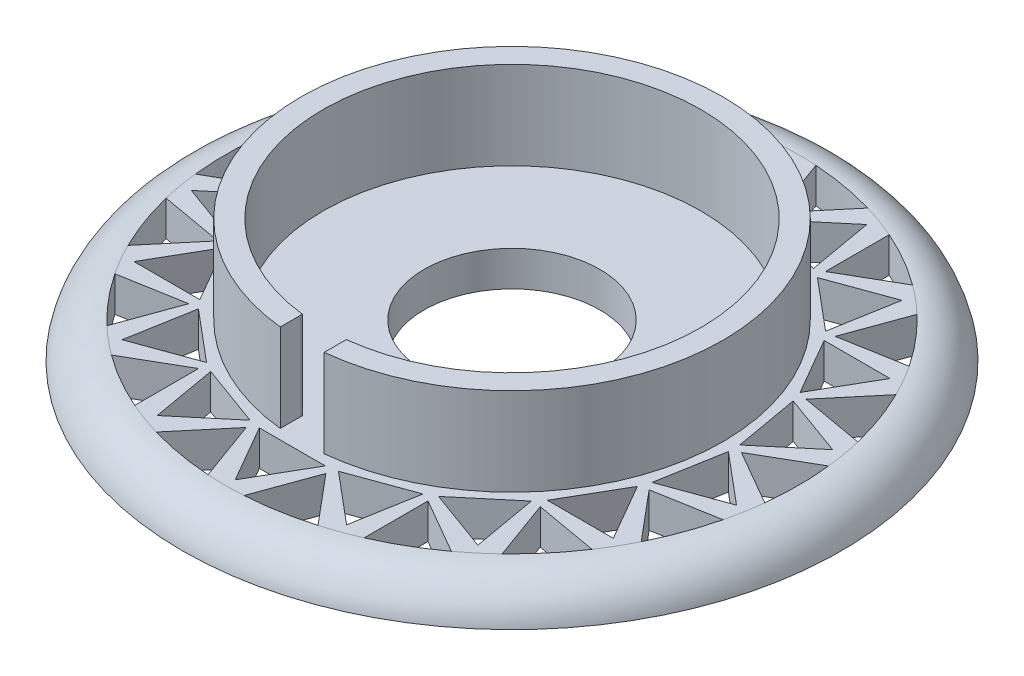
SolidWorks part; units mm, degrees
ref_plane "Front Plane" through (0, 0, 0) normal (0, 0, 1) x (1, 0, 0)
ref_plane "Top Plane" through (0, 0, 0) normal (0, 1, 0) x (1, 0, 0)
ref_plane "Right Plane" through (0, 0, 0) normal (1, 0, 0) x (0, 0, -1)
sketch "Sketch1" plane through (0, 0, 0) normal (0, 1, 0) x (1, 0, 0)
  circle A0 centre (0, 0) radius 75
  dimension "D1" = 150
extrude "Boss-Extrude1" add sketch "Sketch1" along normal blind 8
sketch "Sketch2" plane through (0, 8, 0) normal (0, 1, 0) x (1, 0, 0)
  circle A0 centre (0, 0) radius 43
  circle A1 centre (0, 0) radius 48
  dimension "D1" = 86
  dimension "D2" = 5
extrude "Boss-Extrude3" add sketch "Sketch2" along normal blind 20
sketch "Sketch7" plane through (0, 28, 0) normal (0, 1, 0) x (1, 0, 0)
  line L0 (-5, -43) -> (0, 0)
  line L1 (-5, -43) -> (5, -43)
  line L2 (-5, -43) -> (-5, -48)
  line L3 (-5, -48) -> (5, -48)
  line L4 (5, -43) -> (5, -48)
  line L5 (0, 0) -> (5, -43)
  circle A0 centre (0, 0) radius 43 construction
  circle A1 centre (0, 0) radius 48 construction
  circle M5 centre (0, 0) radius 48
  circle M6 centre (0, 0) radius 43
  dimension "D1" = 10
extrude "Cut-Extrude2" cut sketch "Sketch7" against normal up to surface (20 mm away) contours L4 L1 L2 M5 | L2 L3 M5 | L4 L3 M5 | L5 L1 M6 | L0 L1 M6 region at (-3.7383, 28, 42.9136) region at (0, 28, 45.4571) region at (3.7383, 28, 42.9136) region at (-3.7507, 28, 47.9217) region at (3.7507, 28, 47.9217) up to face at (0, 8, 48)
fillet "Fillet1" radius 10 1 edges at (0, 8, 75)
sketch "Sketch8" plane through (0, 8, 0) normal (0, 1, 0) x (1, 0, 0)
  line L0 (0, 0) -> (-65.202, 0) construction
  line L1 (-52.2117, 0) -> (-65.202, -7.5)
  line L2 (-65.202, -7.5) -> (-65.202, 7.5)
  line L3 (-65.202, 7.5) -> (-52.2117, 0)
  line L4 (-62.0334, 10.9382) -> (-50.5427, 1.2964)
  line L5 (-50.5427, 1.2964) -> (-47.938, 16.0685)
  line L6 (-47.938, 16.0685) -> (-62.0334, 10.9382)
  line L7 (-62.0334, 10.9382) -> (0, 0) construction
  circle A0 centre (0, 0) radius 65.202 construction
  arc A4 (5.2083, -49.728) -> (-5.2083, -49.728) centre (0, 0) ccw
  arc A5 (5.2083, -49.728) -> (-5.2083, -49.728) centre (0, 0) ccw construction
  point P0 (-49.2404, 8.6824)
  circle M10 centre (0, 0) radius 65.202
  dimension "D1" = 15
  dimension "D2" = 10
  dimension "D3" = 2
extrude "Cut-Extrude3" cut sketch "Sketch8" against normal through all contours L3 L1 M10 | L5 L6 L4 region at (-60.781, 8, 0) region at (-53.5047, 8, -9.4343)
pattern_circular "CirPattern1" count 18 over 360 about axis through (0, 28, 0) along (0, -1, 0) of "Cut-Extrude3"
sketch "Sketch9" plane through (0, 8, 0) normal (0, 1, 0) x (1, 0, 0)
  circle A0 centre (0, 0) radius 20
  dimension "D1" = 40
extrude "Cut-Extrude4" cut sketch "Sketch9" against normal through all
